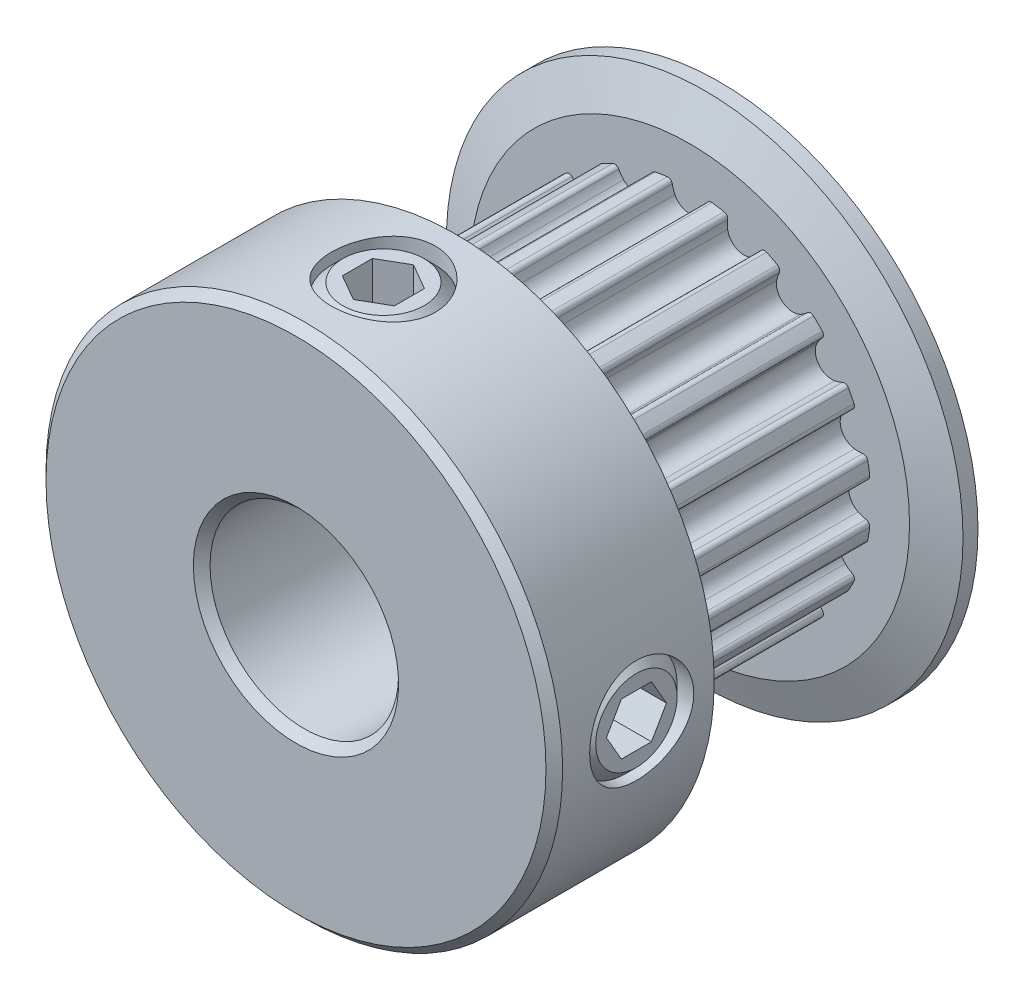
SolidWorks part; units mm, degrees
ref_plane "Front Plane" through (0, 0, 0) normal (0, 0, 1) x (1, 0, 0)
ref_plane "Top Plane" through (0, 0, 0) normal (0, 1, 0) x (1, 0, 0)
ref_plane "Right Plane" through (0, 0, 0) normal (1, 0, 0) x (0, 0, -1)
sketch "Sketch1" plane through (0, 0, 0) normal (0, 0, 1) x (1, 0, 0)
  line L1 (-1.7499, 5.3585) -> (1.7499, 5.3585) construction
  line L4 (0, 0) -> (0, 5.3585) construction
  line L5 (0, 5.3585) -> (0, 11.2111) construction
  line L6 (0, 6.3625) -> (1.9751, 6.0482) construction
  line L7 (1.9751, 6.0482) -> (2.6648, 5.8229) construction
  line L8 (1.9751, 6.0482) -> (1.7499, 5.3585) construction
  line L9 (-1.9751, 6.0482) -> (-1.7499, 5.3585) construction
  line L10 (-1.8963, 5.8067) -> (-2.841, 8.6995)
  line L11 (-2.841, 8.6995) -> (2.841, 8.6995)
  line L12 (2.841, 8.6995) -> (1.8963, 5.8067)
  circle A0 centre (0, 0) radius 6.3625 construction
  circle A1 centre (0, 0) radius 8.6995 construction
  circle A2 centre (0, 0) radius 6.1085 construction
  arc A3 (-0.4989, 5.6703) -> (0.4989, 5.6703) centre (0, 5.9135) ccw
  arc A4 (-0.4989, 5.6703) -> (-0.5855, 5.9387) centre (0.4, 6.1085) cw
  arc A5 (-1.8963, 5.8067) -> (-0.7518, 6.0621) centre (0, 0) cw
  arc A6 (-0.5855, 5.9387) -> (-0.7518, 6.0621) centre (-0.7333, 5.9132) ccw
  arc A7 (1.8963, 5.8067) -> (0.7518, 6.0621) centre (0, 0) ccw
  arc A8 (0.5855, 5.9387) -> (0.7518, 6.0621) centre (0.7333, 5.9132) cw
  arc A9 (0.4989, 5.6703) -> (0.5855, 5.9387) centre (-0.4, 6.1085) ccw
  point P6 (0, 20.9083)
  point P11 (0, 6.3625)
  point P13 (0, 8.6995)
  point P14 (0, 6.1085)
  dimension "D1" = 9.6972
  dimension "D2" = 4.8486
sketch "Sketch2" plane through (0, 0, 0) normal (1, 0, 0) x (0, 0, -1)
  line L0 (-7.135, 3.175) -> (7.135, 3.175)
  line L1 (-7.135, 3.175) -> (-7.135, 8.6995)
  line L2 (-1.75, 8.6995) -> (-7.135, 8.6995)
  line L3 (-2.255, 3.175) -> (-2.255, 8.6995) construction
  line L4 (-2.255, 8.6995) -> (-1.245, 8.6995) construction
  line L5 (-1.245, 8.6995) -> (-1.245, 6.1085) construction
  line L6 (-1.245, 6.1085) -> (6.125, 6.1085)
  line L7 (6.125, 6.1085) -> (6.125, 8.6995) construction
  line L8 (6.125, 8.6995) -> (7.135, 8.6995) construction
  line L9 (7.135, 8.6995) -> (7.135, 3.175)
  line L10 (-7.135, 0) -> (7.135, 0) construction
  line L11 (6.63, 8.6995) -> (6.125, 7.404)
  line L12 (-1.245, 7.404) -> (-1.75, 8.6995)
  line L14 (-1.245, 7.404) -> (-1.245, 6.1085)
  line L15 (6.125, 6.1085) -> (6.125, 7.404)
  line L16 (6.63, 8.6995) -> (7.135, 8.6995)
  arc A0 (-1.245, 7.404) -> (-1.75, 8.6995) centre (-3.1592, 7.404) ccw construction
  arc A1 (6.125, 7.404) -> (6.63, 8.6995) centre (8.0392, 7.404) cw construction
  point P12 (-1.245, 7.404)
  point P14 (-1.75, 8.6995)
  point P20 (6.125, 7.404)
  point P21 (6.63, 8.6995)
  point P25 (6.125, 0)
  point P26 (-1.245, 0)
  dimension "OA" = 14.27
  dimension "Bore" = 6.35
  dimension "Outside Width" = 8.38
  dimension "Inside Width" = 7.37
revolve "Revolve1" add sketch "Sketch2" angle 360 mid plane about L10
sketch "Sketch3" plane through (0, 0, 0) normal (0, 0, 1) x (1, 0, 0)
  line L6 (2.841, 8.6995) -> (-2.841, 8.6995)
  line L7 (1.8963, 5.8067) -> (2.841, 8.6995)
  line L8 (-2.841, 8.6995) -> (-1.8963, 5.8067)
  line L9 (2.841, 8.6995) -> (-2.841, 8.6995)
  line L10 (1.8963, 5.8067) -> (2.841, 8.6995)
  line L11 (-2.841, 8.6995) -> (-1.8963, 5.8067)
  arc A8 (1.8963, 5.8067) -> (0.7518, 6.0621) centre (0, 0) ccw
  arc A9 (0.7518, 6.0621) -> (0.5855, 5.9387) centre (0.7333, 5.9132) ccw
  arc A10 (0.4989, 5.6703) -> (0.5855, 5.9387) centre (-0.4, 6.1085) ccw
  arc A11 (-0.4989, 5.6703) -> (0.4989, 5.6703) centre (0, 5.9135) ccw
  arc A12 (-0.5855, 5.9387) -> (-0.4989, 5.6703) centre (0.4, 6.1085) ccw
  arc A13 (-0.5855, 5.9387) -> (-0.7518, 6.0621) centre (-0.7333, 5.9132) ccw
  arc A14 (-0.7518, 6.0621) -> (-1.8963, 5.8067) centre (0, 0) ccw
  arc A15 (1.8963, 5.8067) -> (0.7518, 6.0621) centre (0, 0) ccw
  arc A16 (0.7518, 6.0621) -> (0.5855, 5.9387) centre (0.7333, 5.9132) ccw
  arc A17 (0.4989, 5.6703) -> (0.5855, 5.9387) centre (-0.4, 6.1085) ccw
  arc A18 (-0.4989, 5.6703) -> (0.4989, 5.6703) centre (0, 5.9135) ccw
  arc A19 (-0.5855, 5.9387) -> (-0.4989, 5.6703) centre (0.4, 6.1085) ccw
  arc A20 (-0.5855, 5.9387) -> (-0.7518, 6.0621) centre (-0.7333, 5.9132) ccw
  arc A21 (-0.7518, 6.0621) -> (-1.8963, 5.8067) centre (0, 0) ccw
  dimension "D1" = 0
extrude "Cut-Extrude1" cut sketch "Sketch3" against normal up to vertex (6.125 mm away) from vertex up to point (0, 6.1085, -6.125) starting at point (0, 6.1085, 1.245)
pattern_circular "CirPattern1" count 20 over 360 about axis through (0, 0, 7.135) along (0, 0, 1) of "Cut-Extrude1"
sketch "Sketch4" plane through (0, 0, 0) normal (1, 0, 0) x (0, -1, 0)
  line L0 (0, -1.245) -> (0, -7.135) construction
  line L1 (-3.175, -7.135) -> (3.175, -7.135) construction
  line L2 (7.404, -1.245) -> (-7.404, -1.245) construction
  circle A0 centre (0, -4.19) radius 1.7526
extrude "Cut-Extrude2" cut sketch "Sketch4" along normal through all
ref_plane "Plane1" through (0, 0, 4.19) normal (0, 0, 1) x (1, 0, 0)
sketch "Sketch5" plane through (0, 0, 4.19) normal (0, 0, 1) x (1, 0, 0)
  line L0 (0, 0) -> (0, 8.6995) construction
  line L1 (3.175, -1.3716) -> (3.175, 0)
  line L2 (3.556, -1.7526) -> (8.1401, -1.7526)
  line L3 (3.175, 0) -> (8.6995, 0) construction
  line L4 (3.175, 0) -> (8.5211, 0)
  line L5 (8.5211, 0) -> (8.5211, -1.3716)
  line L6 (3.556, -1.7526) -> (3.175, -1.3716)
  line L7 (8.5211, -1.3716) -> (8.1401, -1.7526)
  circle A0 centre (0, 0) radius 8.6995 construction
  circle A1 centre (0, 0) radius 3.175 construction
  point P2 (3.175, -1.7526)
  point P11 (8.5211, -1.7526)
revolve "Revolve2" add sketch "Sketch5" angle 360 mid plane about L4
sketch "Sketch6" plane through (8.5211, 5.3841, 0) normal (-1, 0, 0) x (0, -1, 0)
  line L1 (5.3841, 5.2019) -> (4.5078, 4.6959)
  line L2 (4.5078, 4.6959) -> (4.5078, 3.6841)
  line L3 (4.5078, 3.6841) -> (5.3841, 3.1781)
  line L4 (5.3841, 3.1781) -> (6.2604, 3.6841)
  line L5 (6.2604, 3.6841) -> (6.2604, 4.6959)
  line L6 (6.2604, 4.6959) -> (5.3841, 5.2019)
  circle A0 centre (5.3841, 4.19) radius 0.8763 construction
  dimension "D1" = 1.7526
extrude "Cut-Extrude3" cut sketch "Sketch6" along normal blind 1.3144
pattern_circular "CirPattern3" count 2 over 90 about axis through (0, 0, 7.135) along (0, 0, 1) of "Cut-Extrude2", "Revolve2", "Cut-Extrude3"
chamfer "Chamfer1" distance 0.2807 angle 45 2 edges at (3.175, 0, 7.135) (8.6995, 0, 7.135)
ref_axis "Center Axis 1" through (0, 0, -7.135) along (0, 0, 1)
ref_plane "Contact Plane 1" through (0, 0, 7.135) normal (0, 0, 1) x (1, 0, 0)
ref_plane "Contact Plane 2" through (0, 0, -7.135) normal (0, 0, -1) x (-1, 0, 0)
equation "\"D2@Sketch1\"= \"D1@Sketch1\" / 2"
equation "\"D1@Sketch6\" = \"Set Screw@Sketch4\" / 2"
equation "\"D1@Cut-Extrude3\" = \"D1@Sketch6\"*.75"
